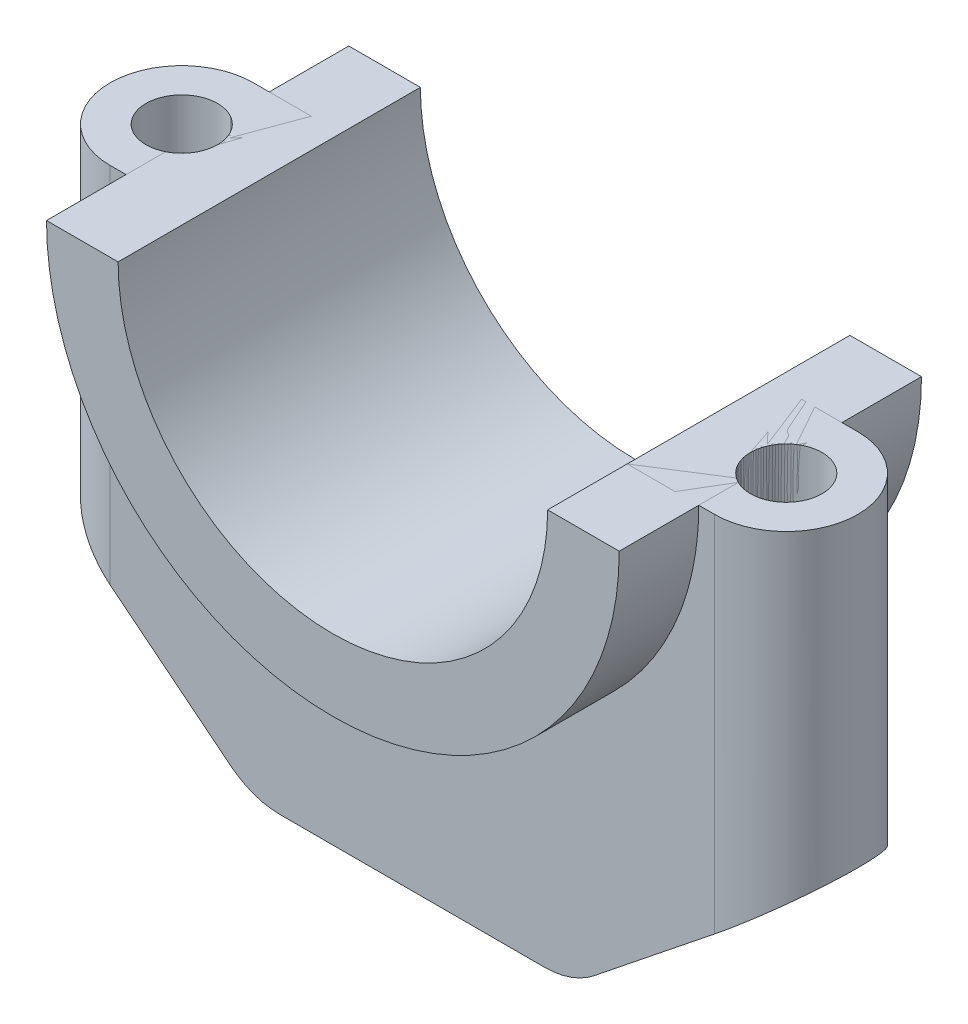
SolidWorks part; units mm, degrees
ref_plane "Front Plane" through (0, 0, 0) normal (0, 0, 1) x (1, 0, 0)
ref_plane "Top Plane" through (0, 0, 0) normal (0, 1, 0) x (1, 0, 0)
ref_plane "Right Plane" through (0, 0, 0) normal (1, 0, 0) x (0, 0, -1)
sketch "Sketch1" plane through (0, 0, 0) normal (0, 0, 1) x (1, 0, 0)
  line L0 (-45.0922, 0) -> (-27, 0)
  line L1 (-45.0922, 0) -> (-45.0922, -40)
  line L2 (-20.0922, -60) -> (20.0922, -60)
  line L3 (45.0922, -40) -> (45.0922, 0)
  line L4 (27, 0) -> (45.0922, 0)
  line L5 (-45.0922, -40) -> (-20.0922, -60)
  line L6 (20.0922, -60) -> (45.0922, -40)
  arc A0 (-36, 0) -> (36, 0) centre (0, 0) ccw
  arc A1 (-27, 0) -> (27, 0) centre (0, 0) ccw
  point P7 (0, 0)
  point P8 (-45.0922, -60)
  point P9 (45.0922, -60)
  dimension "D2" = 72
  dimension "D3" = 54
  dimension "D1" = 60
  dimension "D4" = 20
  dimension "D5" = 25
  dimension "D6" = 25
  dimension "D7" = 20
extrude "Boss-Extrude1" add sketch "Sketch1" along normal mid plane 18 contours A0 L0 L1 L5 L2 L6 L3 L4 | A1 L0 A0 L4 region at (0, -36.3652, 0) region at (-31.5, -0.805, 0)
extrude "Boss-Extrude2" add sketch "Sketch1<4>" along normal mid plane 38 separate body contours A1 L0 A0 L4 region at (-31.5, -0.805, 0)
sketch "Sketch1<4>" plane through (0, 0, 0) normal (0, 0, 1) x (1, 0, 0) same geometry as "Sketch1"
sketch "Sketch3" plane through (0, 0, 0) normal (0, 1, 0) x (1, 0, 0)
  line L0 (-36, 19) -> (-27, 19)
  line L1 (-27, 19) -> (-27, -19)
  line L2 (-27, -19) -> (-36, -19)
  line L3 (-36, -19) -> (-36.0461, -9)
  line L4 (-45.0922, -9) -> (-27, -9) construction
  line L5 (-36.0461, -9) -> (-38, -9)
  line L7 (-38, 9) -> (-36.0461, 9)
  line L8 (-45.0922, 9) -> (-27, 9) construction
  line L9 (-36.0461, 9) -> (-36, 19)
  line L10 (27, 19) -> (27, -19)
  line L11 (27, -19) -> (36, -19)
  line L12 (36, -19) -> (36.0461, -9)
  line L13 (27, -9) -> (45.0922, -9) construction
  line L14 (36.0461, -9) -> (38, -9)
  line L16 (38, 9) -> (36.0461, 9)
  line L17 (27, 9) -> (45.0922, 9) construction
  line L18 (36.0461, 9) -> (36, 19)
  line L19 (36, 19) -> (27, 19)
  line L20 (-38, 9) -> (-45.0922, 9)
  line L21 (-45.0922, 9) -> (-45.0922, 5.5409)
  line L22 (-45.0922, -9) -> (-38, -9)
  line L23 (38, -9) -> (45.0922, -9)
  line L24 (45.0922, -9) -> (45.0922, -5.5409)
  line L25 (45.0922, 9) -> (38, 9)
  line L26 (-45.0922, -5.5409) -> (-45.0922, -9)
  line L27 (45.0922, 5.5409) -> (45.0922, 9)
  line L28 (45.0922, 9) -> (45.0922, -9)
  circle A0 centre (-38, 0) radius 4.5
  circle A1 centre (38, 0) radius 4.5
  arc A2 (-38, 9) -> (-38, -9) centre (-38, 0) ccw
  arc A3 (38, -9) -> (38, 9) centre (38, 0) ccw
  line M19 (-27, 9) -> (-45.0922, 9)
  line M20 (-45.0922, 9) -> (-45.0922, -9)
  line M21 (-45.0922, -9) -> (-27, -9)
  dimension "D1" = 18
  dimension "D2" = 9
  dimension "D3" = 9
  dimension "D4" = 18
  dimension "D5" = 76
  dimension "D6" = 38
  dimension "D7" = 38
extrude "Cut-Extrude1" cut sketch "Sketch3" against normal blind 60 contours A0 | A1
extrude "Cut-Extrude2" cut sketch "Sketch3<4>" against normal blind 60 contours A2 M19 M20 | A2 M20 M21 | A3 L23 L24 | A3 L24 L25 region at (-43.3945, 0, -8.0084) region at (-43.3945, 0, 8.0084) region at (43.3945, 0, -8.0084) region at (43.3945, 0, 8.0084)
sketch "Sketch3<4>" plane through (0, 0, 0) normal (0, 1, 0) x (1, 0, 0) same geometry as "Sketch3"
extrude "Boss-Extrude4" add sketch "Sketch3<6>" against normal blind 60 contours A2 M20 | L28 A3 region at (-45.8627, 0, 0) region at (45.8627, 0, 0)
sketch "Sketch3<6>" plane through (0, 0, 0) normal (0, 1, 0) x (1, 0, 0) same geometry as "Sketch3"
sketch "Sketch6" plane through (0, 0, 0) normal (0, 0, 1) x (1, 0, 0)
  line L0 (-20.0922, -60) -> (-62.464, -26.1026)
  line L1 (-62.464, -26.1026) -> (-62.464, -60)
  line L2 (-62.464, -60) -> (-20.0922, -60)
  line L3 (20.0922, -60) -> (65.9219, -23.3362)
  line L4 (65.9219, -23.3362) -> (69.8191, -60)
  line L5 (69.8191, -60) -> (20.0922, -60)
  line L6 (-38, -45.6737) -> (-20.0922, -60) construction
  line L7 (20.0922, -60) -> (38, -45.6737) construction
extrude "Cut-Extrude3" cut sketch "Sketch6" against normal mid plane 60
fillet "Fillet1" radius 10 2 edges at (20.0922, -60, 0) (-20.0922, -60, 0)
